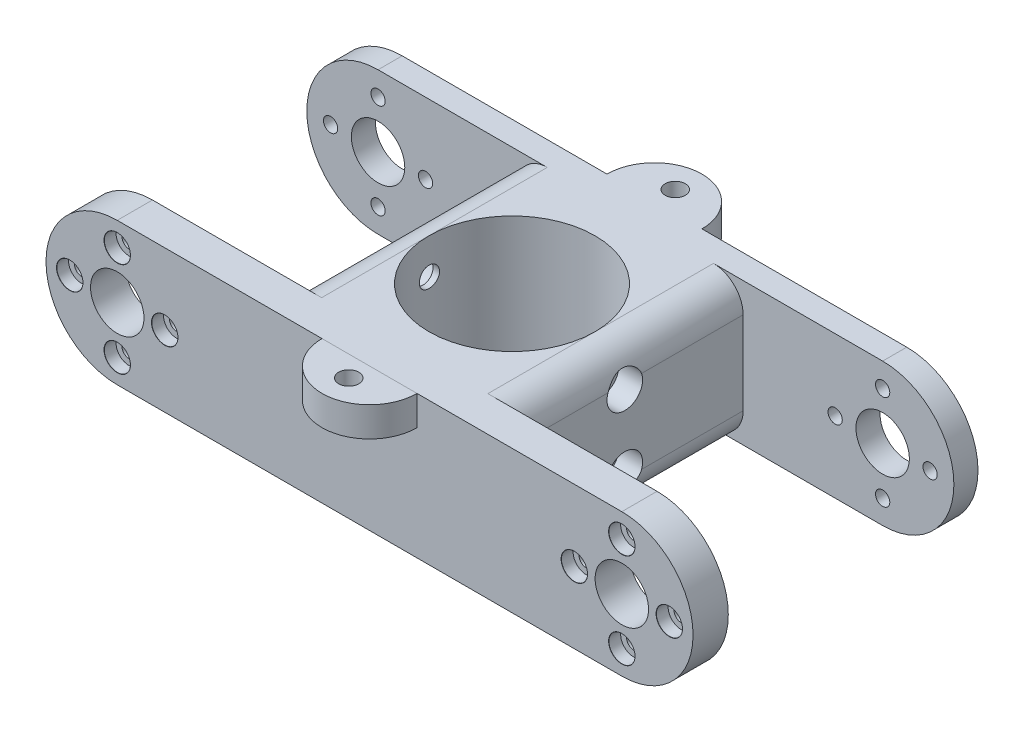
SolidWorks part; units mm, degrees
material "PET"
ref_plane "Front Plane" through (0, 0, 0) normal (0, 0, 1) x (1, 0, 0)
ref_plane "Top Plane" through (0, 0, 0) normal (0, 1, 0) x (1, 0, 0)
ref_plane "Right Plane" through (0, 0, 0) normal (1, 0, 0) x (0, 0, -1)
sketch "Sketch1" plane through (0, 0, 0) normal (0, 0, 1) x (1, 0, 0)
  line L1 (-42.5, 12) -> (42.5, 12)
  line L3 (-42.5, -12) -> (42.5, -12)
  arc A0 (-42.5, 12) -> (-42.5, -12) centre (-42.5, 0) ccw
  arc A1 (42.5, -12) -> (42.5, 12) centre (42.5, 0) ccw
  point P6 (0, 12)
  dimension "D2" = 12
  dimension "D1" = 85
extrude "Boss-Extrude1" add sketch "Sketch1" along normal blind 48
sketch "Sketch2" plane through (0, 0, 48) normal (0, 0, 1) x (1, 0, 0)
  line L0 (-42.5, -8) -> (-42.5, 8) construction
  line L1 (-50.5, 0) -> (-34.5, 0) construction
  line L2 (34.5, 0) -> (50.5, 0) construction
  line L3 (42.5, 8) -> (42.5, -8) construction
  circle A0 centre (-42.5, 0) radius 8 construction
  circle A1 centre (42.5, 0) radius 8 construction
  dimension "D1" = 16
  dimension "D2" = 16
hole_wizard "CBORE for M2 SHCS1" positions "3DSketch2" profile "Sketch4" counterbore size "M2" standard "ANSI Metric" end condition through all
sketch3d "3DSketch2"
  point P0 (-42.5, 8, 48)
  point P3 (-34.5, 0, 48)
  point P6 (-42.5, -8, 48)
  point P9 (-50.5, 0, 48)
  point P12 (34.5, 0, 48)
  point P15 (50.5, 0, 48)
  point P19 (42.5, 8, 48)
  point P22 (42.5, -8, 48)
sketch "Sketch4" plane through (-42.5, 8, 48) normal (1, 0, 0) x (0, -1, 0)
  line L0 (0, 0) -> (0, 48)
  line L1 (0, 48) -> (1.2, 48)
  line L3 (1.2, 48) -> (1.2, 2)
  line L4 (2.2, 2) -> (1.2, 2)
  line L5 (2.2, 2) -> (2.2, 0.025)
  line L6 (2.2, 0.025) -> (2.225, 0)
  line L7 (2.225, 0) -> (0, 0)
  line L8 (-2.2, 0.025) -> (-2.225, 0) construction
  line L11 (0, -6.35) -> (0, 107.95) construction
  dimension "Thru Hole Dia." = 2.4
  dimension "Thru Hole Depth" = 48
  dimension "C'Bore Dia." = 4.4
  dimension "C'Bore Depth" = 2
  dimension "Near C'Sink Dia." = 4.45
  dimension "Near C'Sink Angle" = 90
sketch "Sketch5" plane through (0, 12, 0) normal (0, 1, 0) x (1, 0, 0)
  line L0 (42.5, -48) -> (42.5, 0) construction
  line L1 (-54.5, 0) -> (-54.5, -48) construction
  line L2 (-54.5, -4.0631) -> (-19, -4.0631)
  line L3 (-54.5, -4.0631) -> (-54.5, -42.0631)
  line L4 (-54.5, -42.0631) -> (-19, -42.0631)
  line L5 (-19, -4.0631) -> (-19, -42.0631)
  line L6 (0, 0) -> (0, -48) construction
  line L7 (42.5, -48) -> (-42.5, -48) construction
  line L8 (54.5, -42.0631) -> (19, -42.0631)
  line L9 (19, -4.0631) -> (19, -42.0631)
  line L10 (54.5, -4.0631) -> (19, -4.0631)
  line L11 (54.5, -4.0631) -> (54.5, -42.0631)
  circle A0 centre (0, -24) radius 14
  point P7 (42.5, -24)
  dimension "D1" = 28
  dimension "D2" = 19
  dimension "D3" = 38
extrude "Cut-Extrude1" cut sketch "Sketch5" against normal through all
sketch "Sketch6" plane through (0, 0, 48) normal (0, 0, 1) x (1, 0, 0)
  line L0 (-50.5, 0) -> (-34.5, 0) construction
  line L1 (34.5, 0) -> (50.5, 0) construction
  circle A0 centre (-42.5, 0) radius 4.5
  circle A1 centre (42.5, 0) radius 4.5
  dimension "D1" = 9
  dimension "D2" = 9
extrude "Cut-Extrude2" cut sketch "Sketch6" against normal through all
sketch "Sketch8" plane through (0, 0, 0) normal (0, 0, -1) x (-1, 0, 0)
  line L0 (50.5, 0) -> (34.5, 0) construction
  line L1 (42.5, -8) -> (42.5, 8) construction
  line L2 (-42.5, 8) -> (-42.5, -8) construction
  line L3 (-34.5, 0) -> (-50.5, 0) construction
  line L4 (50.5, 0) -> (34.5, 0) construction
  line L5 (42.5, -8) -> (42.5, 8) construction
  line L6 (-42.5, 8) -> (-42.5, -8) construction
  line L7 (-34.5, 0) -> (-50.5, 0) construction
  circle A0 centre (42.5, 0) radius 8 construction
  circle A1 centre (-42.5, 0) radius 8 construction
  circle A2 centre (42.5, 0) radius 8 construction
  circle A3 centre (-42.5, 0) radius 8 construction
hole_wizard "CBORE for M2 SHCS2" positions "3DSketch4" profile "Sketch9" counterbore size "M2" standard "ANSI Metric" end condition through all
sketch3d "3DSketch4"
  point P0 (42.5, 8, 0)
  point P3 (50.5, 0, 0)
  point P6 (34.5, 0, 0)
  point P9 (42.5, -8, 0)
  point P12 (-42.5, 8, 0)
  point P15 (-50.5, 0, 0)
  point P18 (-42.5, -8, 0)
  point P21 (-34.5, 0, 0)
sketch "Sketch9" plane through (42.5, 8, 0) normal (1, 0, 0) x (0, 1, 0)
  line L0 (0, 0) -> (0, 48)
  line L1 (0, 48) -> (1.2, 48)
  line L3 (1.2, 48) -> (1.2, 2)
  line L4 (2.2, 2) -> (1.2, 2)
  line L5 (2.2, 2) -> (2.2, 0.025)
  line L6 (2.2, 0.025) -> (2.225, 0)
  line L7 (2.225, 0) -> (0, 0)
  line L8 (-2.2, 0.025) -> (-2.225, 0) construction
  line L11 (0, -6.35) -> (0, 107.95) construction
  dimension "Thru Hole Dia." = 2.4
  dimension "Thru Hole Depth" = 48
  dimension "C'Bore Dia." = 4.4
  dimension "C'Bore Depth" = 2
  dimension "Near C'Sink Dia." = 4.45
  dimension "Near C'Sink Angle" = 90
fillet "Fillet1" radius 5 4 edges at (-19, -12, 23.0631) (19, -12, 23.0631) (19, 12, 23.0631) (-19, 12, 23.0631)
sketch "Sketch10" plane through (-19, 0, 0) normal (-1, 0, 0) x (0, 0, 1)
  line L0 (24, 12) -> (24, -12) construction
  point P4 (24, 6)
  point P5 (24, -6)
  point P6 (24, 0)
  dimension "D1" = 6
  dimension "D2" = 6
hole_wizard "CBORE for M3 SHCS1" positions "3DSketch5" profile "Sketch11" counterbore size "M3" standard "ANSI Metric" end condition through all
sketch3d "3DSketch5"
  point P0 (-19, 6, 24)
  point P3 (-19, -6, 24)
sketch "Sketch11" plane through (-19, 6, 24) normal (0, 1, 0) x (0, 0, 1)
  line L0 (0, 0) -> (0, 73.5)
  line L1 (0, 73.5) -> (1.7, 73.5)
  line L3 (1.7, 73.5) -> (1.7, 4)
  line L4 (3.25, 4) -> (1.7, 4)
  line L5 (3.25, 4) -> (3.25, 0.025)
  line L6 (3.25, 0.025) -> (3.275, 0)
  line L7 (3.275, 0) -> (0, 0)
  line L8 (-3.25, 0.025) -> (-3.275, 0) construction
  line L11 (0, -6.35) -> (0, 107.95) construction
  dimension "Thru Hole Dia." = 3.4
  dimension "Thru Hole Depth" = 73.5
  dimension "C'Bore Dia." = 6.5
  dimension "C'Bore Depth" = 4
  dimension "Near C'Sink Dia." = 6.55
  dimension "Near C'Sink Angle" = 90
sketch "Sketch12" plane through (19, 0, 0) normal (1, 0, 0) x (0, 0, -1)
  circle A0 centre (-24, 6) radius 3
  circle A1 centre (-24, -6) radius 3
  dimension "D1" = 6
extrude "Cut-Extrude3" cut sketch "Sketch12" against normal blind 4
sketch "Sketch13" plane through (0, 12, 0) normal (0, 1, 0) x (1, 0, 0)
  line L0 (42.5, -48) -> (-42.5, -48) construction
  line L1 (-8, -48) -> (8, -48)
  arc A0 (-8, -48) -> (8, -48) centre (0, -48) ccw
  dimension "D1" = 8
extrude "Boss-Extrude2" add sketch "Sketch13" against normal blind 5 separate body
ref_plane "Plane1" through (0, 0, 24) normal (0, 0, 1) x (1, 0, 0)
sketch "Sketch14" plane through (0, 12, 0) normal (0, 1, 0) x (1, 0, 0)
  line L0 (42.5, -48) -> (-42.5, -48) construction
  line L1 (8, -48) -> (-8, -48) construction
  circle A0 centre (0, -51.5) radius 1.7
  point P0 (0, -51.5)
  point P6 (0, -48)
  dimension "D2" = 3.4
  dimension "D1" = 3.5
extrude "Cut-Extrude7" cut sketch "Sketch14" against normal blind 5
mirror "Mirror6" about plane through (0, 0, 24) normal (0, 0, 1) of "Cut-Extrude7", "Boss-Extrude2"
